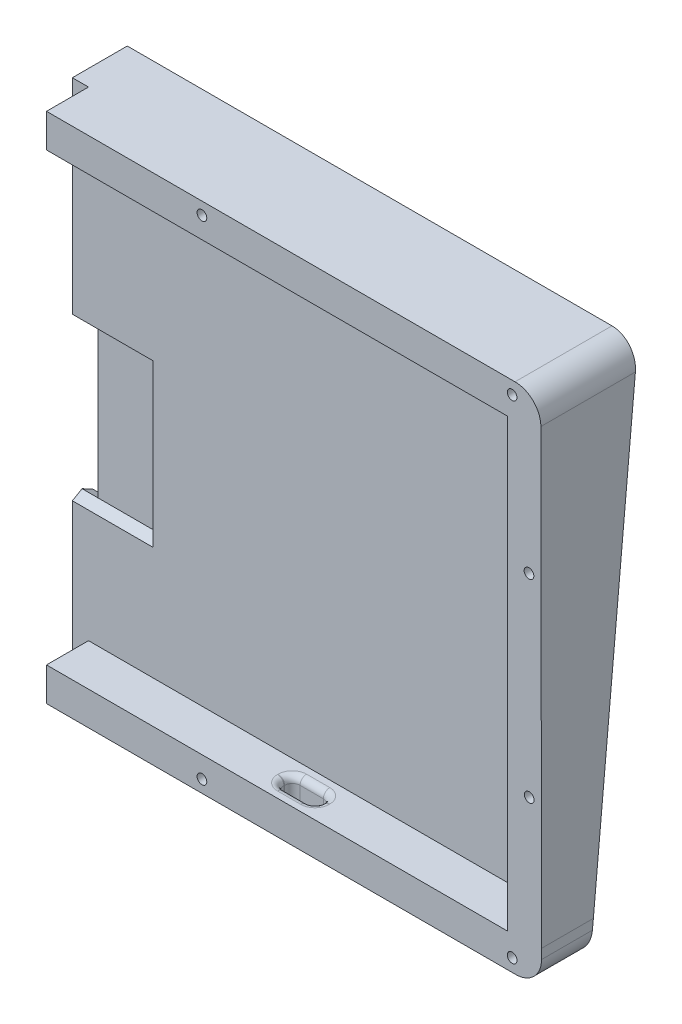
SolidWorks part; units mm, degrees
ref_plane "Front Plane" through (0, 0, 0) normal (0, 0, 1) x (1, 0, 0)
ref_plane "Top Plane" through (0, 0, 0) normal (0, 1, 0) x (1, 0, 0)
ref_plane "Right Plane" through (0, 0, 0) normal (1, 0, 0) x (0, 0, -1)
sketch "Model" plane through (0, 0, 0) normal (0, 0, 1) x (1, 0, 0)
  line L0 (0, 11) -> (0, 150.75)
  line L1 (306.2071, 11.0112) -> (306.0112, 150.7612)
  line L2 (298.0112, 158.75) -> (8, 158.75)
  line L3 (0, 11) -> (0, 8)
  line L4 (8, 0) -> (298.2071, 0)
  line L5 (306.2071, 11.0112) -> (306.2071, 8)
  line L6 (295.63, 10.37) -> (10.37, 10.37)
  line L7 (10.37, 10.37) -> (10.37, 148.38)
  line L8 (10.37, 148.38) -> (295.63, 148.38)
  line L9 (295.63, 148.38) -> (295.63, 10.37)
  arc A0 (8, 158.75) -> (0, 150.75) centre (8, 150.75) ccw
  arc A1 (306.0112, 150.7612) -> (298.0112, 158.75) centre (298.0112, 150.75) ccw
  arc A2 (0, 8) -> (8, 0) centre (8, 8) ccw
  arc A3 (298.2071, 0) -> (306.2071, 8) centre (298.2071, 8) ccw
  circle A4 centre (105.1086, 3.75) radius 1.5
  circle A5 centre (9.1086, 3.75) radius 1.5
  circle A6 centre (201.1085, 3.8173) radius 1.5
  circle A7 centre (297.1084, 3.9518) radius 1.5
  circle A8 centre (105.1086, 155) radius 1.5
  circle A9 centre (9.1086, 155) radius 1.5
  circle A10 centre (201.1085, 154.9327) radius 1.5
  circle A11 centre (297.1084, 154.7982) radius 1.5
  circle A12 centre (3.75, 109.375) radius 1.5
  circle A13 centre (3.75, 49.375) radius 1.5
  circle A14 centre (302.3189, 109.5842) radius 1.5
  circle A15 centre (302.403, 49.5843) radius 1.5
sketch "草图2" plane through (0, 0, 0) normal (0, 0, 1) x (1, 0, 0)
  line L0 (0, 11) -> (0, 150.75)
  line L1 (306.2071, 11.0112) -> (306.0112, 150.7612)
  line L2 (298.0112, 158.75) -> (8, 158.75)
  line L3 (0, 11) -> (0, 8)
  line L4 (8, 0) -> (298.2071, 0)
  line L5 (306.2071, 11.0112) -> (306.2071, 8)
  line L6 (295.63, 10.37) -> (10.37, 10.37)
  line L7 (10.37, 10.37) -> (10.37, 148.38)
  line L8 (10.37, 148.38) -> (295.63, 148.38)
  line L9 (295.63, 148.38) -> (295.63, 10.37)
  arc A0 (8, 158.75) -> (0, 150.75) centre (8, 150.75) ccw
  arc A1 (306.0112, 150.7612) -> (298.0112, 158.75) centre (298.0112, 150.75) ccw
  arc A2 (0, 8) -> (8, 0) centre (8, 8) ccw
  arc A3 (298.2071, 0) -> (306.2071, 8) centre (298.2071, 8) ccw
  circle A4 centre (105.1086, 3.75) radius 1.5
  circle A5 centre (9.1086, 3.75) radius 1.5
  circle A6 centre (201.1085, 3.8173) radius 1.5
  circle A7 centre (297.1084, 3.9518) radius 1.5
  circle A8 centre (105.1086, 155) radius 1.5
  circle A9 centre (9.1086, 155) radius 1.5
  circle A10 centre (201.1085, 154.9327) radius 1.5
  circle A11 centre (297.1084, 154.7982) radius 1.5
  circle A12 centre (3.75, 109.375) radius 1.5
  circle A13 centre (3.75, 49.375) radius 1.5
  circle A14 centre (302.3189, 109.5842) radius 1.5
  circle A15 centre (302.403, 49.5843) radius 1.5
sketch "草图3" plane through (0, 0, 0) normal (0, 0, 1) x (1, 0, 0)
  line L0 (0, 11) -> (0, 150.75)
  line L1 (306.2071, 11.0112) -> (306.0112, 150.7612)
  line L2 (298.0112, 158.75) -> (8, 158.75)
  line L3 (0, 11) -> (0, 8)
  line L4 (8, 0) -> (298.2071, 0)
  line L5 (306.2071, 11.0112) -> (306.2071, 8)
  line L6 (295.63, 10.37) -> (10.37, 10.37)
  line L7 (10.37, 10.37) -> (10.37, 148.38)
  line L8 (10.37, 148.38) -> (295.63, 148.38)
  line L9 (295.63, 148.38) -> (295.63, 10.37)
  arc A0 (8, 158.75) -> (0, 150.75) centre (8, 150.75) ccw
  arc A1 (306.0112, 150.7612) -> (298.0112, 158.75) centre (298.0112, 150.75) ccw
  arc A2 (0, 8) -> (8, 0) centre (8, 8) ccw
  arc A3 (298.2071, 0) -> (306.2071, 8) centre (298.2071, 8) ccw
  circle A4 centre (105.1086, 3.75) radius 1.5
  circle A5 centre (9.1086, 3.75) radius 1.5
  circle A6 centre (201.1085, 3.8173) radius 1.5
  circle A7 centre (297.1084, 3.9518) radius 1.5
  circle A8 centre (105.1086, 155) radius 1.5
  circle A9 centre (9.1086, 155) radius 1.5
  circle A10 centre (201.1085, 154.9327) radius 1.5
  circle A11 centre (297.1084, 154.7982) radius 1.5
  circle A12 centre (3.75, 109.375) radius 1.5
  circle A13 centre (3.75, 49.375) radius 1.5
  circle A14 centre (302.3189, 109.5842) radius 1.5
  circle A15 centre (302.403, 49.5843) radius 1.5
sketch "草图4" plane through (0, 0, 0) normal (0, 0, 1) x (1, 0, 0)
  line L0 (0, 11) -> (0, 150.75)
  line L1 (306.2071, 11.0112) -> (306.0112, 150.7612)
  line L2 (298.0112, 158.75) -> (8, 158.75)
  line L3 (0, 11) -> (0, 8)
  line L4 (8, 0) -> (298.2071, 0)
  line L5 (306.2071, 11.0112) -> (306.2071, 8)
  line L6 (295.63, 10.37) -> (10.37, 10.37)
  line L7 (10.37, 10.37) -> (10.37, 148.38)
  line L8 (10.37, 148.38) -> (295.63, 148.38)
  line L9 (295.63, 148.38) -> (295.63, 10.37)
  arc A0 (8, 158.75) -> (0, 150.75) centre (8, 150.75) ccw
  arc A1 (306.0112, 150.7612) -> (298.0112, 158.75) centre (298.0112, 150.75) ccw
  arc A2 (0, 8) -> (8, 0) centre (8, 8) ccw
  arc A3 (298.2071, 0) -> (306.2071, 8) centre (298.2071, 8) ccw
  circle A4 centre (105.1086, 3.75) radius 1.5
  circle A5 centre (9.1086, 3.75) radius 1.5
  circle A6 centre (201.1085, 3.8173) radius 1.5
  circle A7 centre (297.1084, 3.9518) radius 1.5
  circle A8 centre (105.1086, 155) radius 1.5
  circle A9 centre (9.1086, 155) radius 1.5
  circle A10 centre (201.1085, 154.9327) radius 1.5
  circle A11 centre (297.1084, 154.7982) radius 1.5
  circle A12 centre (3.75, 109.375) radius 1.5
  circle A13 centre (3.75, 49.375) radius 1.5
  circle A14 centre (302.3189, 109.5842) radius 1.5
  circle A15 centre (302.403, 49.5843) radius 1.5
extrude "凸台-拉伸1" add sketch "Model" against normal blind 30 contours L2 A0 L0 L3 A2 L4 A3 L5 L1 A1
extrude "切除-拉伸1" cut sketch "草图2" against normal blind 5 contours A4 | A5 | A10 | A11 | A7 | A6 | A13 | A12 | A8 | A9 | A14 | A15
sketch "草图6" plane through (0, 0, 0) normal (-1, 0, 0) x (0, 0, 1)
  line L0 (-30, 158.75) -> (-30, 0)
  line L1 (-30, 0) -> (-15, 0)
  line L2 (-30, 0) -> (0, 0) construction
  line L3 (-15, 0) -> (-30, 158.75)
extrude "切除-拉伸4" cut sketch "草图6" against normal blind 307 contours L3 L0 L1
extrude "切除-拉伸5" cut sketch "草图3" against normal blind 13 contours L8 L9 L6 L7
sketch "草图8" plane through (0, 0, 0) normal (0, 0, 1) x (1, 0, 0)
  line L0 (10.37, 148.38) -> (10.37, 129.38)
  line L1 (10.37, 10.37) -> (10.37, 148.38) construction
  line L2 (10.37, 129.38) -> (0, 129.38)
  line L3 (0, 11) -> (0, 150.75) construction
  line L4 (0, 129.38) -> (0, 118.38)
  line L5 (0, 118.38) -> (10.37, 118.38)
  line L6 (295.63, 10.37) -> (232.13, 10.37)
  line L7 (295.63, 10.37) -> (10.37, 10.37) construction
  line L8 (232.13, 10.37) -> (232.13, 0)
  line L9 (8, 0) -> (298.2071, 0) construction
  line L10 (232.13, 0) -> (220.13, 0)
  line L11 (220.13, 0) -> (220.13, 10.37)
  line L12 (220.13, 10.37) -> (232.13, 10.37)
  line L13 (10.37, 118.38) -> (10.37, 129.38)
sketch "草图9" plane through (0, 0, -13) normal (0, 0, 1) x (1, 0, 0)
  line L5 (25.37, 128.38) -> (125.37, 128.38)
  line L6 (25.37, 128.38) -> (25.37, 48.38)
  line L7 (25.37, 48.38) -> (125.37, 48.38)
  line L8 (125.37, 128.38) -> (125.37, 48.38)
sketch "草图12" plane through (0, 0, -13) normal (0, 0, 1) x (1, 0, 0)
  line L11 (133, 45.37) -> (173, 45.37)
  line L12 (133, 45.37) -> (133, 95.37)
  line L13 (133, 95.37) -> (173, 95.37)
  line L14 (173, 45.37) -> (173, 95.37)
extrude "切除-拉伸7" cut sketch "草图12" against normal blind 3 draft 30
extrude "切除-拉伸8" cut sketch "草图9" against normal blind 3 draft 30 contours L5 L8 L7 L6
sketch "草图14" plane through (0, 0, 0) normal (-1, 0, 0) x (0, 0, 1)
  line L6 (-5.9, 129.38) -> (-6.1, 129.38)
  line L7 (-3.5, 126.98) -> (-3.5, 120.78)
  line L8 (-5.9, 118.38) -> (-6.1, 118.38)
  line L9 (-8.5, 126.98) -> (-8.5, 120.78)
  arc A0 (-6.1, 118.38) -> (-8.5, 120.78) centre (-6.1, 120.78) cw
  arc A1 (-5.9, 118.38) -> (-3.5, 120.78) centre (-5.9, 120.78) ccw
  arc A2 (-3.5, 126.98) -> (-5.9, 129.38) centre (-5.9, 126.98) ccw
  arc A3 (-8.5, 126.98) -> (-6.1, 129.38) centre (-6.1, 126.98) cw
  point P12 (0, 0)
  dimension "D1" = 2.4
extrude "切除-拉伸9" cut sketch "草图14" against normal blind 11 contours L7 A1 L8 A0 L9 A3 L6 A2
fillet "圆角1" radius 2 8 edges at (0, 128.6771, -7.7971) (0, 129.38, -6) (0, 128.6771, -4.2029) (0, 123.88, -3.5) (0, 119.0829, -4.2029) (0, 118.38, -6) (0, 119.0829, -7.7971) (0, 123.88, -8.5)
sketch "草图15" plane through (0, 0, 0) normal (0, -1, 0) x (1, 0, 0)
  line L6 (222.53, -3.9597) -> (229.73, -3.9597)
  line L7 (220.13, -6.3597) -> (220.13, -6.5597)
  line L8 (222.53, -8.9597) -> (229.73, -8.9597)
  line L9 (232.13, -6.3597) -> (232.13, -6.5597)
  arc A0 (220.13, -6.5597) -> (222.53, -8.9597) centre (222.53, -6.5597) ccw
  arc A1 (232.13, -6.5597) -> (229.73, -8.9597) centre (229.73, -6.5597) cw
  arc A2 (232.13, -6.3597) -> (229.73, -3.9597) centre (229.73, -6.3597) ccw
  arc A3 (222.53, -3.9597) -> (220.13, -6.3597) centre (222.53, -6.3597) ccw
  dimension "D1" = 2.4
extrude "切除-拉伸10" cut sketch "草图15" against normal blind 11 contours L6 A2 L9 A1 L8 A0 L7 A3
fillet "圆角2" radius 2 8 edges at (232.13, 0, -6.4597) (231.4271, 0, -4.6626) (226.13, 0, -3.9597) (220.8329, 0, -4.6626) (220.13, 0, -6.4597) (220.8329, 0, -8.2567) (226.13, 0, -8.9597) (231.4271, 0, -8.2567)
fillet "圆角3" radius 2 8 edges at (10.37, 129.38, -6) (10.37, 128.6771, -4.2029) (10.37, 123.88, -3.5) (10.37, 119.0829, -4.2029) (10.37, 118.38, -6) (10.37, 119.0829, -7.7971) (10.37, 123.88, -8.5) (10.37, 128.6771, -7.7971)
fillet "圆角4" radius 2 8 edges at (231.4271, 10.37, -8.2567) (232.13, 10.37, -6.4597) (231.4271, 10.37, -4.6626) (226.13, 10.37, -3.9597) (220.8329, 10.37, -4.6626) (220.13, 10.37, -6.4597) (220.8329, 10.37, -8.2567) (226.13, 10.37, -8.9597)
sketch "草图17" plane through (0, 158.75, 0) normal (0, 1, 0) x (1, 0, 0)
  line L0 (153.0056, 30) -> (153.0056, 0)
  line L1 (298.0112, 30) -> (8, 30) construction
  line L2 (298.0112, 0) -> (8, 0) construction
sketch "草图18" plane through (0, 0, 0) normal (0, -1, 0) x (1, 0, 0)
  line L0 (153.0056, 0) -> (153.0056, -15)
  line L1 (153.0056, -30) -> (153.0056, 0) construction
ref_plane "基准面1" through (153.0056, 0, 0) normal (1, 0, 0) x (0, 0, -1)
split "分割1" trim tools "基准面1" bodies to split 111 resulting bodies 112 113
delete or keep bodies "实体-删除/保留 3" type delete bodies bodies 113
sketch "草图19" plane through (153.0056, 0, 0) normal (-1, 0, 0) x (0, 0, 1)
  line L4 (-30, 158.75) -> (-24.0113, 95.37)
  line L5 (-13, 148.38) -> (-13, 95.37)
  line L6 (-15, 0) -> (-30, 158.75) construction
  line L9 (-19.2869, 45.37) -> (-15, 0)
  line L13 (-13, 10.37) -> (-13, 45.37)
  line L14 (-13, 95.37) -> (-16, 93.6379)
  line L15 (-16, 93.6379) -> (-24.0113, 95.37)
  line L16 (-13, 45.37) -> (-16, 47.1021)
  line L17 (-16, 47.1021) -> (-19.2869, 45.37)
  line L18 (-13, 10.37) -> (-13, 0)
  line L19 (-15, 0) -> (0, 0) construction
  line L20 (-13, 0) -> (-15, 0)
  line L21 (-13, 148.38) -> (-13, 158.75)
  line L22 (0, 158.75) -> (-30, 158.75) construction
  line L23 (-13, 158.75) -> (-30, 158.75)
extrude "凸台-拉伸3" add sketch "草图19" along normal blind 5 contours L9 L20 L18 L13 L16 L17
extrude "凸台-拉伸4" add sketch "草图19<5>" along normal blind 5
sketch "草图19<5>" plane through (153.0056, 0, 0) normal (-1, 0, 0) x (0, 0, 1) same geometry as "草图19"
